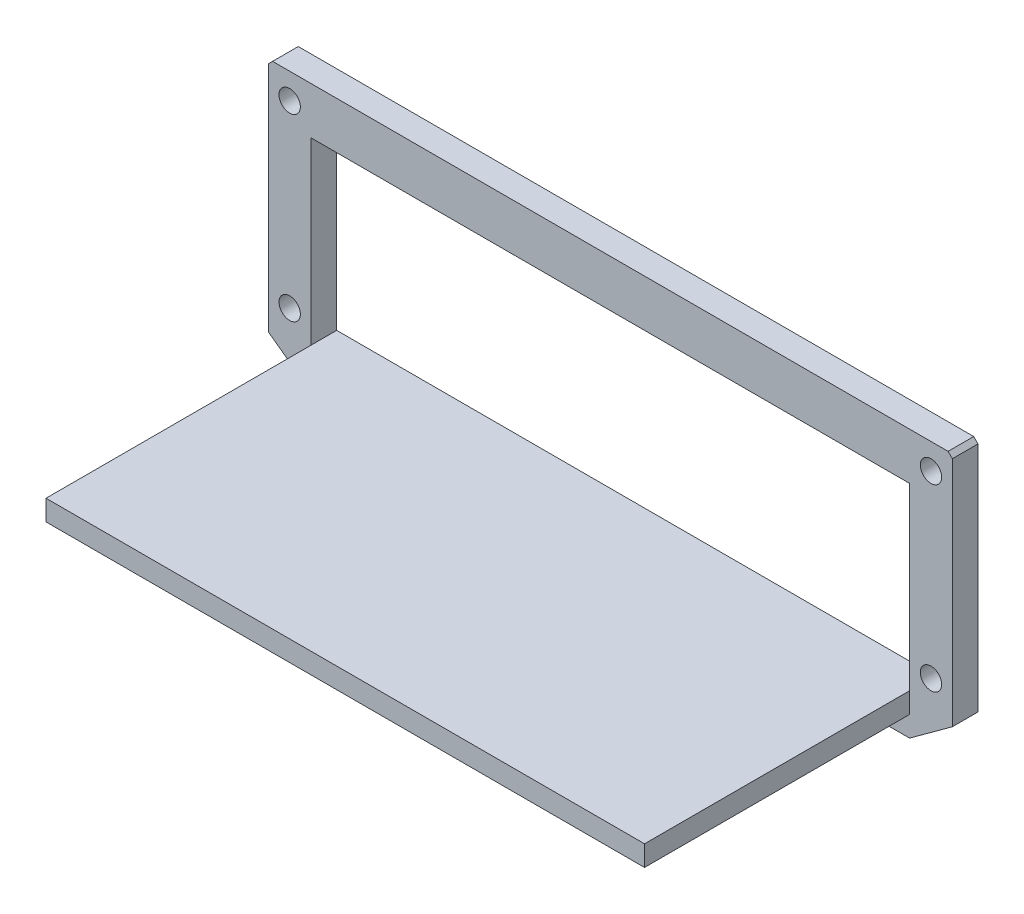
SolidWorks part; units mm, degrees
note: The reader was unsure of these and kept them because the rebuilt part matched: shared geometry of "草图13<2>".
material "45"
ref_plane "前视基准面" through (0, 0, 0) normal (0, 0, 1) x (1, 0, 0)
ref_plane "上视基准面" through (0, 0, 0) normal (0, 1, 0) x (1, 0, 0)
ref_plane "右视基准面" through (0, 0, 0) normal (1, 0, 0) x (0, 0, -1)
sketch "草图1" plane through (0, 0, 0) normal (0, 0, 1) x (1, 0, 0)
  line L0 (0, 17) -> (0, -17) construction
  line L1 (-40, 17) -> (40, 17)
  line L2 (-40, 17) -> (-40, -17)
  line L3 (-40, -17) -> (40, -17)
  line L4 (40, 17) -> (40, -17)
  dimension "D1" = 80
  dimension "D2" = 34
extrude "拉伸1" add sketch "草图1" along normal blind 3
sketch "草图2" plane through (0, 0, 3) normal (0, 0, 1) x (1, 0, 0)
  line L0 (0, 11.5) -> (0, -11.5) construction
  line L1 (-35, 11.5) -> (35, 11.5)
  line L2 (-35, 11.5) -> (-35, -11.5)
  line L3 (-35, -11.5) -> (35, -11.5)
  line L4 (35, 11.5) -> (35, -11.5)
  dimension "D1" = 23
  dimension "D2" = 70
extrude "拉伸2" cut sketch "草图2" against normal up to surface (3 mm away) up to face at (0, 0, 0)
sketch "草图3" plane through (0, 0, 0) normal (0, 0, 1) x (1, 0, 0)
  line L0 (0, 14) -> (0, -7) construction
  line L1 (-37.5, 14) -> (37.5, 14) construction
  line L2 (-37.5, 14) -> (-37.5, -7) construction
  line L3 (-37.5, -7) -> (37.5, -7) construction
  line L4 (37.5, 14) -> (37.5, -7) construction
  line L5 (40, 17) -> (-40, 17) construction
  circle A0 centre (-37.5, 14) radius 1.5
  circle A1 centre (-37.5, -7) radius 1.5
  circle A2 centre (37.5, 14) radius 1.5
  circle A3 centre (37.5, -7) radius 1.5
  dimension "D3" = 3
  dimension "D1" = 75
  dimension "D2" = 21
  dimension "D4" = 3
extrude "拉伸3" [suppressed] cut sketch "草图3" against normal blind 4
sketch "草图4" [suppressed] plane through (0, -17, 0) normal (0, -1, 0) x (1, 0, 0)
  line L0 (47, 3) -> (27, 3) construction
  line L1 (47, 6) -> (47, 0) construction
  dimension "D1" = 20
hole_wizard "打孔尺寸根据内六角圆柱头螺钉的类型1" [suppressed] positions "3D草图1" profile "草图5" counterbore size "M2.5" standard "GB"
sketch3d "3D草图1" [suppressed]
  point P0 (27, -17, 3)
sketch "草图5" plane through (27, -17, 3) normal (1, 0, 0) x (0, 0, -1)
  line L0 (0, 0) -> (0, 10.8712)
  line L1 (0, 10.8712) -> (1.45, 10)
  line L2 (1.45, 10) -> (1.45, 1.5)
  line L3 (1.45, 1.5) -> (2.5, 1.5)
  line L4 (2.5, 1.5) -> (2.5, 0)
  line L5 (2.5, 0) -> (0, 0)
  line L10 (0, 10.8712) -> (-1.45, 10) construction
  line L11 (0, -6.35) -> (0, 107.95) construction
  dimension "孔直径" = 2.9
  dimension "孔深度" = 10
  dimension "柱形沉头孔直径" = 5
  dimension "柱形沉头孔深度" = 1.5
  dimension "导头角度" = 118
mirror "镜向1" [suppressed] about plane through (0, 0, 0) normal (0, 1, 0)
sketch "草图6" plane through (0, 0, 0) normal (0, 0, 1) x (1, 0, 0)
  line L0 (32, 14) -> (32, -14) construction
  line L1 (0, 0) -> (32, 0) construction
  circle A0 centre (32, 14) radius 1.5
  circle A1 centre (32, -14) radius 1.5
  dimension "D2" = 3
  dimension "D1" = 28
  dimension "D3" = 32
extrude "拉伸4" [suppressed] cut sketch "草图6" against normal blind 10
fillet "圆角1" [suppressed] radius 1
chamfer "倒角1" distance 0.5 angle 45 2 edges at (-40, 17, 1.5) (40, 17, 1.5)
sketch "草图7" plane through (0, 0, 3) normal (0, 0, 1) x (1, 0, 0)
  line L1 (-12.5, -14) -> (12.5, -14)
  line L2 (-12.5, -14) -> (-12.5, -17)
  line L3 (-12.5, -17) -> (12.5, -17)
  line L4 (12.5, -14) -> (12.5, -17)
  line L5 (0, 0) -> (0, -17) construction
  line L6 (-40, -17) -> (40, -17) construction
  dimension "D1" = 3
  dimension "D2" = 25
extrude "拉伸6" cut sketch "草图7" against normal up to surface (3 mm away) up to face at (0, 0, 0)
fillet "圆角2" radius 2 2 edges at (12.5, -14, 1.5) (-12.5, -14, 1.5)
chamfer "倒角2" distance 11 angle 30 1 edges at (40, -17, 1.5) first distance on face at (26.25, -17, 1.5)
chamfer "倒角3" distance 11 angle 30 1 edges at (-40, -17, 1.5) first distance on face at (-26.25, -17, 1.5)
fillet "圆角3" radius 2 2 edges at (12.5, -17, 1.5) (-12.5, -17, 1.5)
hole_wizard "打孔尺寸根据十字槽沉头木螺钉的类型1" [suppressed] positions "3D草图2" profile "草图8" countersink size "M2.5" standard "GB"
sketch3d "3D草图2"
  point P0 (32, 14, 0)
  point P3 (32, -14, 0)
sketch "草图8" plane through (32, 14, 0) normal (1, 0, 0) x (0, 1, 0)
  line L0 (0, 0) -> (0, 3)
  line L1 (0, 3) -> (1.45, 3)
  line L2 (1.45, 3) -> (1.45, 1.25)
  line L3 (1.45, 1.25) -> (2.7, 0)
  line L5 (2.7, 0) -> (0, 0)
  line L6 (-1.45, 1.25) -> (-2.7, 0) construction
  line L11 (0, -6.35) -> (0, 107.95) construction
  dimension "通孔孔直径" = 2.9
  dimension "通孔孔深度" = 3
  dimension "近端锥形沉头孔直径" = 5.4
  dimension "近端锥形沉头孔角度" = 90
hole_wizard "Ø2.5 (2.5) 直径孔1" positions "3D草图3" profile "草图9" hole size "Ø2.5" standard "GB" end condition through all
sketch3d "3D草图3"
  point P0 (-37.5, -7, 0)
  point P3 (-37.5, 14, 0)
  point P6 (37.5, 14, 0)
  point P9 (37.5, -7, 0)
sketch "草图9" plane through (-37.5, -7, 0) normal (1, 0, 0) x (0, 1, 0)
  line L0 (0, 0) -> (0, 3)
  line L1 (0, 3) -> (1.25, 3)
  line L2 (1.25, 3) -> (1.25, 0)
  line L5 (1.25, 0) -> (0, 0)
  line L11 (0, -6.35) -> (0, 107.95) construction
  dimension "Thru Hole Dia." = 2.5
  dimension "Thru Hole Depth" = 3
sketch "Sketch1" plane through (0, 0, 0) normal (0, 0, -1) x (-1, 0, 0)
  line L0 (-40, -10.6491) -> (-40, 16.5) construction
  line L1 (-40, 8) -> (40, 8)
  line L2 (-40, 8) -> (-40, 17)
  line L3 (-40, 17) -> (40, 17)
  line L4 (40, 8) -> (40, 17)
  line L5 (-39.5, 17) -> (39.5, 17) construction
  line L6 (40, 16.5) -> (40, -10.6491) construction
  line L7 (-14.373, -17) -> (-29, -17) construction
  dimension "D1" = 25
extrude "Extrude1" [suppressed] cut sketch "Sketch1" against normal blind 10
sketch "Sketch2" plane through (0, 0, 0) normal (0, 0, -1) x (-1, 0, 0)
  line L0 (-35, -11.5) -> (35, -11.5) construction
  line L1 (-26, -11.5) -> (-23, -11.5)
  line L2 (-26, -11.5) -> (-26, 6.5)
  line L3 (-26, 6.5) -> (-23, 6.5)
  line L4 (-23, -11.5) -> (-23, 6.5)
  line L5 (-40, -10.6491) -> (-40, 16.5) construction
  dimension "D1" = 3
  dimension "D2" = 14
  dimension "D3" = 18
extrude "Extrude2" [suppressed] add sketch "Sketch2" against normal up to surface (3 mm away)
sketch "Sketch3" plane through (0, 0, 3) normal (0, 0, -1) x (-1, 0, 0)
  line L0 (-40, -10.6491) -> (-40, 16.5) construction
  line L1 (-40, 2.5) -> (40, 2.5)
  line L2 (-40, 2.5) -> (-40, -2.5)
  line L3 (-40, -2.5) -> (40, -2.5)
  line L4 (40, 2.5) -> (40, -2.5)
  line L5 (40, 16.5) -> (40, -10.6491) construction
  line L6 (-39.5, 17) -> (39.5, 17) construction
  dimension "D1" = 14.5
  dimension "D2" = 5
extrude "Extrude3" [suppressed] cut sketch "Sketch3" along normal blind 1.2
sketch "草图10" plane through (0, 0, 3) normal (0, 0, 1) x (1, 0, 0)
  line L0 (39.5, 17) -> (-39.5, 17) construction
  line L1 (-35, 11.5) -> (35, 11.5)
  line L2 (-35, 11.5) -> (-35, 17)
  line L3 (-35, 17) -> (35, 17)
  line L4 (35, 11.5) -> (35, 17)
  line L5 (35, -11.5) -> (35, 11.5) construction
extrude "凸台-拉伸1" [suppressed] add sketch "草图10" along normal blind 0.5
sketch "草图11" plane through (0, 0, 3) normal (0, 0, 1) x (1, 0, 0)
  line L0 (-34.5, -13.8246) -> (34.5, -13.8246)
  line L1 (-40, -10.6491) -> (-29, -17) construction
  line L2 (29, -17) -> (40, -10.6491) construction
  line L3 (34.5, -13.8246) -> (34.5, -24.0056)
  line L4 (34.5, -24.0056) -> (-34.5, -24.0056)
  line L5 (-34.5, -24.0056) -> (-34.5, -13.8246)
extrude "切除-拉伸1" cut sketch "草图11" against normal blind 10
sketch "草图12" plane through (0, 0, 3) normal (0, 0, 1) x (1, 0, 0)
  line L6 (-40, -10.6491) -> (-34.5, -13.8246)
  line L8 (-40, -10.6491) -> (-34.5, -13.8246) construction
  line L10 (-35, -14.3) -> (-40, -10.6491)
  line L11 (-35, -14.3) -> (35, -14.3)
  line L12 (-34.5, -13.8246) -> (34.5, -13.8246)
  line L13 (34.5, -13.8246) -> (40, -10.6491) construction
  line L14 (34.5, -13.8246) -> (-34.5, -13.8246) construction
  line L15 (34.5, -13.8246) -> (40, -10.6491)
  line L16 (40, -10.6491) -> (35, -14.3)
extrude "凸台-拉伸2" add sketch "草图12" against normal blind 3
sketch "草图13" plane through (0, 0, 3) normal (0, 0, 1) x (1, 0, 0)
  line L8 (-35, -11.5) -> (-35, -9.5)
  line L9 (-35, 11.5) -> (-35, -11.5) construction
  line L10 (-35, -9.5) -> (35, -9.5)
  line L11 (35, -11.5) -> (35, 11.5) construction
  line L13 (-35, -11.5) -> (-35, -11.9)
  line L14 (-35, -11.9) -> (35, -11.9)
  line L15 (35, -11.9) -> (35, -9.5)
extrude "凸台-拉伸4" add sketch "草图13" against normal blind 3
extrude "凸台-拉伸5" add sketch "草图13<2>" along normal blind 31
sketch "草图13<2>" plane through (0, 0, 3) normal (0, 0, 1) x (1, 0, 0) same geometry as "草图13"
